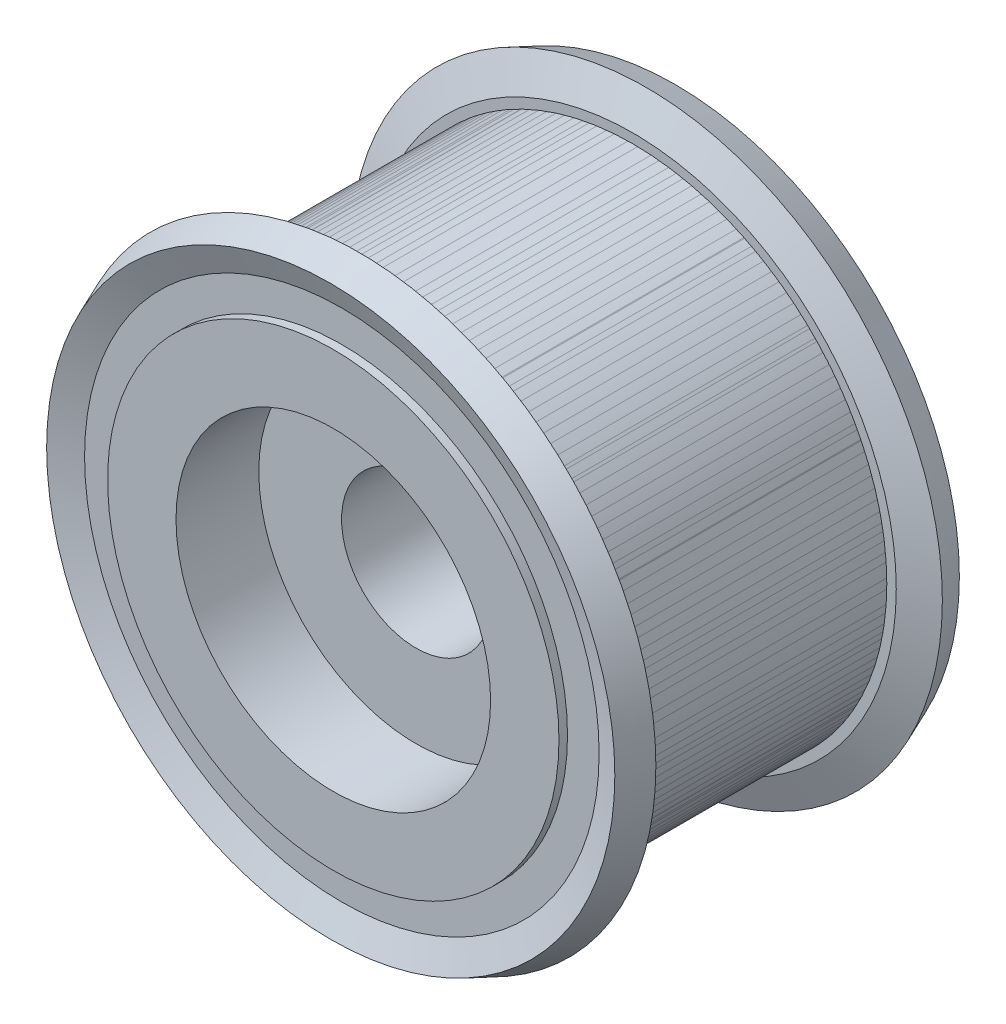
SolidWorks part; units mm, degrees
material "6061 合金"
ref_plane "前视基准面" through (0, 0, 0) normal (0, 0, 1) x (1, 0, 0)
ref_plane "上视基准面" through (0, 0, 0) normal (0, 1, 0) x (1, 0, 0)
ref_plane "右视基准面" through (0, 0, 0) normal (1, 0, 0) x (0, 0, -1)
ref_axis "基准轴1" through (0, 0, 55) along (0, 0, -1)
sketch "SketchRevolveGearBelt01" plane through (0, 0, 0) normal (1, 0, 0) x (0, 0, -1)
  line L0 (0, 0) -> (1, 0) construction
  line L1 (10.2489, 0) -> (10.2489, 13.6295)
  line L2 (10.2489, 13.6295) -> (9.7333, 13.6295)
  line L3 (9.7333, 13.6295) -> (9.7333, 15.5381)
  line L4 (9.7333, 15.5381) -> (10.4042, 17.1579)
  line L5 (10.4042, 17.1579) -> (8.6513, 17.884)
  line L6 (8.6513, 17.884) -> (7.8359, 15.9155)
  line L7 (7.8359, 15.9155) -> (7.8359, 15.344)
  line L8 (7.8359, 15.344) -> (-7.8359, 15.344)
  line L9 (-7.8359, 15.344) -> (-7.8359, 15.9155)
  line L10 (-7.8359, 15.9155) -> (-8.6513, 17.884)
  line L11 (-8.6513, 17.884) -> (-10.4042, 17.1579)
  line L12 (-10.4042, 17.1579) -> (-9.7333, 15.5381)
  line L13 (-9.7333, 15.5381) -> (-9.7333, 13.6295)
  line L14 (-9.7333, 13.6295) -> (-10.2489, 13.6295)
  line L15 (-10.2489, 13.6295) -> (-10.2489, 0)
  line L16 (-10.2489, 0) -> (10.2489, 0)
  dimension "GearBeltFlange1OutsideLength" = 1.9086
  dimension "GearBeltFlange1X" = 0.6709
  dimension "GearBeltFlange1Y" = 1.6198
  dimension "GearBeltFlangeThickness" = 1.8974
  dimension "GearBeltFlangeInside" = 0.5715
  dimension "GearBeltOutsideDiameter" = 15.344
  dimension "GearBeltFlange2X" = 0.6709
revolve "GearBelt01" add sketch "SketchRevolveGearBelt01" angle 360 about L0
sketch "SketchToothGearBelt01" plane through (0, 0, 0) normal (0, 0, 1) x (1, 0, 0)
  arc A0 (15.1892, 2.17) -> (15.1892, -2.17) centre (0, 0) cw
  spline S0 degree 3 poles (15.1892, -2.17) (15.1933, -2.1413) (15.1958, -2.0978) (15.1916, -2.0399) (15.1848, -1.997) (15.1743, -1.9547) (15.1603, -1.9136) (15.1428, -1.8738) (15.1219, -1.8356) (15.0979, -1.7993) (15.0709, -1.7653) (15.041, -1.7336) (15.0086, -1.7046) (14.9738, -1.6785) (14.9369, -1.6555) (14.8981, -1.6357) (14.8578, -1.6193) (14.8163, -1.6064) (14.7738, -1.5971) (14.7307, -1.5914) (14.6736, -1.5894) (14.5978, -1.5908) (14.5033, -1.5873) (14.4043, -1.5753) (14.3065, -1.5557) (14.2106, -1.5285) (14.1171, -1.4939) (14.0266, -1.452) (13.9397, -1.4032) (13.8569, -1.3477) (13.7786, -1.2859) (13.7055, -1.2181) (13.6379, -1.1449) (13.5762, -1.0665) (13.5209, -0.9836) (13.4722, -0.8965) (13.4305, -0.806) (13.396, -0.7124) (13.369, -0.6164) (13.3496, -0.5186) (13.3376, -0.4196) (13.3342, -0.2999) (13.3356, -0.16) (13.3351, 0) (13.3356, 0.16) (13.3342, 0.2999) (13.3376, 0.4196) (13.3496, 0.5186) (13.369, 0.6164) (13.396, 0.7124) (13.4305, 0.806) (13.4722, 0.8965) (13.5209, 0.9836) (13.5762, 1.0665) (13.6379, 1.1449) (13.7055, 1.2181) (13.7786, 1.2859) (13.8569, 1.3477) (13.9397, 1.4032) (14.0266, 1.452) (14.1171, 1.4939) (14.2106, 1.5285) (14.3065, 1.5557) (14.4043, 1.5753) (14.5033, 1.5873) (14.5978, 1.5908) (14.6736, 1.5894) (14.7307, 1.5914) (14.7738, 1.5971) (14.8163, 1.6064) (14.8578, 1.6193) (14.8981, 1.6357) (14.9369, 1.6555) (14.9738, 1.6785) (15.0086, 1.7046) (15.041, 1.7336) (15.0709, 1.7653) (15.0979, 1.7993) (15.1219, 1.8356) (15.1428, 1.8738) (15.1603, 1.9136) (15.1743, 1.9547) (15.1848, 1.997) (15.1916, 2.0399) (15.1958, 2.0978) (15.1933, 2.1413) (15.1892, 2.17) knots 0 0 0 0 0.013305 0.019957 0.026609 0.033261 0.039914 0.046566 0.053218 0.059871 0.066523 0.073175 0.079828 0.08648 0.093132 0.099784 0.106437 0.113089 0.119741 0.126394 0.133046 0.145958 0.16121 0.176462 0.191714 0.206966 0.222218 0.23747 0.252722 0.267974 0.283226 0.298478 0.31373 0.328983 0.344235 0.359487 0.374739 0.389991 0.405243 0.420495 0.435747 0.450999 0.4755 0.5 0.5245 0.549001 0.564253 0.579505 0.594757 0.610009 0.625261 0.640513 0.655765 0.671017 0.68627 0.701522 0.716774 0.732026 0.747278 0.76253 0.777782 0.793034 0.808286 0.823538 0.83879 0.854042 0.866954 0.873606 0.880259 0.886911 0.893563 0.900216 0.906868 0.91352 0.920172 0.926825 0.933477 0.940129 0.946782 0.953434 0.960086 0.966739 0.973391 0.980043 0.986695 1 1 1 1
extrude "ToothExtrudeCutGearBelt01" cut sketch "SketchToothGearBelt01" against normal blind 7.8359 and the other way blind 7.8359
pattern_circular "PatternGearBelt01" count 20 every 18 about axis through (0, 0, 55) along (0, 0, -1) of "ToothExtrudeCutGearBelt01"
sketch "AuxiliarySketchGearBelt01" plane through (0, 0, 0) normal (0, 0, 1) x (1, 0, 0)
  circle A0 centre (0, 0) radius 15.9155 construction
  dimension "PitchDiameter" = 31.831
sketch "草图1" plane through (0, 0, 10.2489) normal (0, 0, 1) x (1, 0, 0)
  circle A0 centre (0, 0) radius 9.5
  dimension "D1" = 19
extrude "切除-拉伸1" cut sketch "草图1" against normal blind 5
mirror "镜向1" about plane through (0, 0, 0) normal (0, 0, 1) of "切除-拉伸1"
sketch "草图2" plane through (0, 0, 5.2489) normal (0, 0, 1) x (1, 0, 0)
  circle A0 centre (0, 0) radius 4.5
  dimension "D1" = 9
extrude "切除-拉伸2" cut sketch "草图2" against normal through all
